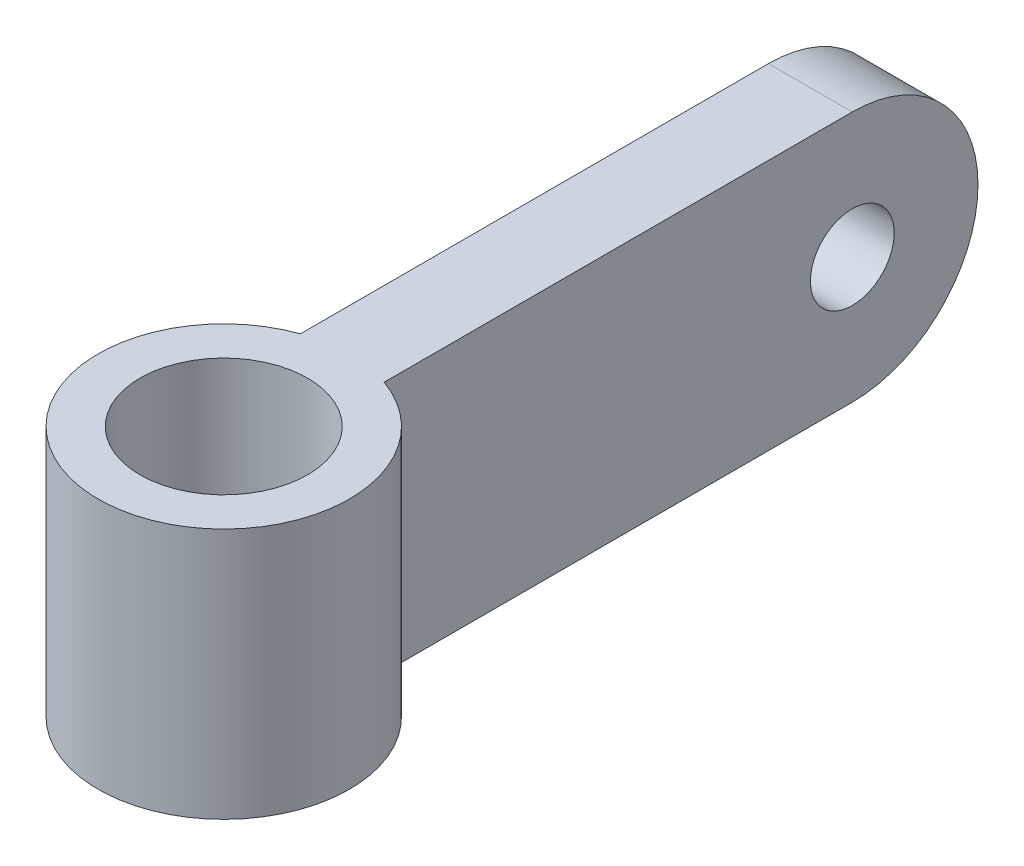
SolidWorks part; units mm, degrees
ref_plane "前视基准面" through (0, 0, 0) normal (0, 0, 1) x (1, 0, 0)
ref_plane "上视基准面" through (0, 0, 0) normal (0, 1, 0) x (1, 0, 0)
ref_plane "右视基准面" through (0, 0, 0) normal (1, 0, 0) x (0, 0, -1)
sketch "草图1" plane through (0, 0, 0) normal (0, 1, 0) x (1, 0, 0)
  circle A0 centre (0, 0) radius 20
  circle A1 centre (0, 0) radius 30
  dimension "D1" = 40
  dimension "D2" = 60
extrude "凸台-拉伸1" add sketch "草图1" along normal mid plane 60
sketch "草图2" plane through (0, 0, 0) normal (1, 0, 0) x (0, 0, -1)
  line L1 (30, 30) -> (170, 30)
  line L2 (30, 30) -> (30, -30)
  line L3 (30, -30) -> (170, -30)
  line L4 (170, 30) -> (170, -30)
  dimension "D1" = 140
extrude "凸台-拉伸2" add sketch "草图2" along normal mid plane 20 separate body
sketch "草图3" plane through (10, 0, 0) normal (1, 0, 0) x (0, 0, -1)
  line L0 (170, -30) -> (170, 30) construction
  circle A0 centre (140, 0) radius 10
  dimension "D1" = 20
  dimension "D2" = 30
extrude "切除-拉伸1" cut sketch "草图3" against normal through all
fillet "圆角1" 2 edges at (0, -30, -170) (0, 30, -170) type full round first side face at (0, -30, -100) second side face at (0, 30, -100) middle face at (0, 0, -170)
sketch "草图4" plane through (0, 0, -30) normal (0, 0, 1) x (1, 0, 0)
  line L4 (-10, 30) -> (-10, -30)
  line L5 (-10, -30) -> (10, -30)
  line L6 (10, -30) -> (10, 30)
  line L7 (10, 30) -> (-10, 30)
  line L8 (-10, 30) -> (-10, -30)
  line L9 (-10, -30) -> (10, -30)
  line L10 (10, -30) -> (10, 30)
  line L11 (10, 30) -> (-10, 30)
  dimension "D1" = 0
extrude "凸台-拉伸3" add sketch "草图4" along normal up to next (10 mm away)
